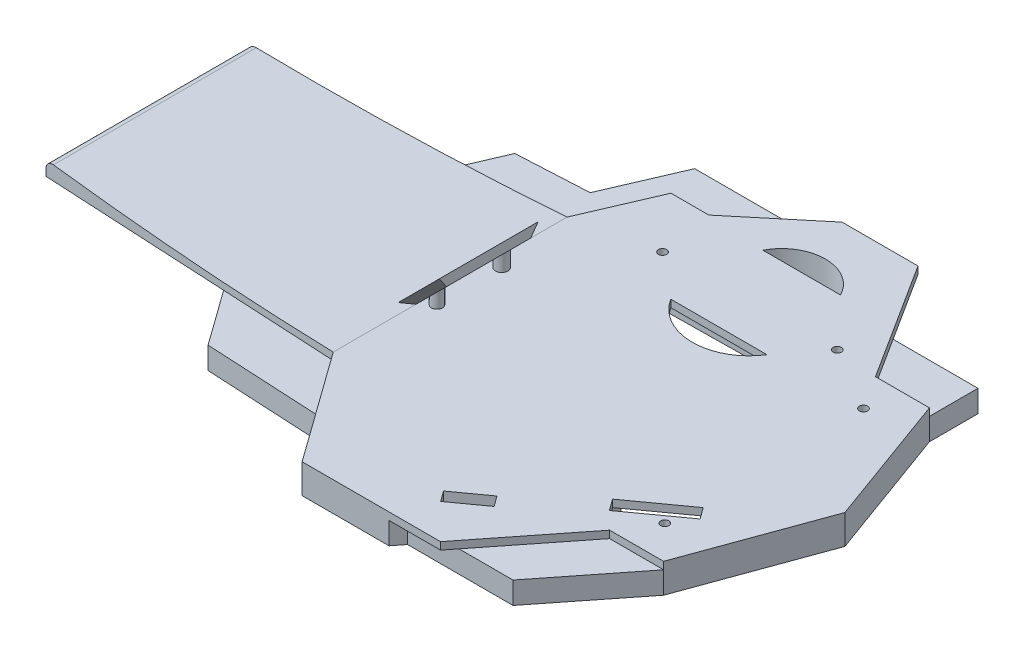
SolidWorks part; units mm, degrees
ref_plane "前视基准面" through (0, 0, 0) normal (0, 0, 1) x (1, 0, 0)
ref_plane "上视基准面" through (0, 0, 0) normal (0, 1, 0) x (1, 0, 0)
ref_plane "右视基准面" through (0, 0, 0) normal (1, 0, 0) x (0, 0, -1)
other "Configuration Table"
sketch "草图2" plane through (0, 0, 0) normal (0, 1, 0) x (1, 0, 0)
  line L0 (0, 0) -> (243.6421, 0) construction
  line L30 (176.8295, 36.1855) -> (82.5273, -31.8251) construction
  line L35 (141.8216, 68.0827) -> (121.1619, 68.0827)
  line L36 (176.8295, 36.1855) -> (190, 0)
  line L37 (104.1466, -61.9173) -> (82.5273, -31.8251)
  line L38 (82.5273, -31.8251) -> (0, -27.5)
  line L39 (0, -27.5) -> (0, 27.5)
  line L40 (0, 27.5) -> (82.5273, 31.8251)
  line L43 (190, 0) -> (176.8295, -36.1855)
  line L45 (82.5273, 31.8251) -> (91.0398, 51.6089)
  line L51 (104.1466, -61.9173) -> (190, 0) construction
  line L53 (141.8216, -61.9173) -> (104.1466, -61.9173)
  line L55 (82.5273, 31.8251) -> (342.4089, 31.8251) construction
  line L57 (176.8295, 36.1855) -> (176.8295, 0) construction
  line L58 (176.8295, 0) -> (176.8295, -36.1855) construction
  line L59 (82.5273, -31.8251) -> (342.4089, -31.8251) construction
  line L62 (91.0398, 51.6089) -> (101.351, 51.6089)
  line L63 (101.351, 51.6089) -> (121.1619, 68.0827)
  line L64 (141.8216, 68.0827) -> (162.1337, 36.1855)
  line L65 (162.1337, 36.1855) -> (176.8295, 36.1855)
  line L66 (176.8295, -36.1855) -> (162.1337, -36.1855)
  line L67 (162.1337, -36.1855) -> (141.8216, -61.9173)
  dimension "D1" = 190
  dimension "D2" = 130
  dimension "D4" = 55
  dimension "D6" = 93
  dimension "D7" = 93
  dimension "D8" = 140
extrude "凸台-拉伸1" add sketch "草图2" along normal blind 2
sketch "草图6" plane through (0, 2, 0) normal (0, 1, 0) x (1, 0, 0)
  line L0 (82.5273, 31.8251) -> (82.5273, -31.8251)
  line L1 (82.5273, -31.8251) -> (0, -27.5)
  line L2 (0, -27.5) -> (0, 27.5)
  line L3 (0, 27.5) -> (82.5273, 31.8251)
extrude "凸台-拉伸2" add sketch "草图6" along normal blind 2
sketch "草图7" plane through (0, 0, 0) normal (0, 0, 1) x (1, 0, 0)
  line L2 (82.5273, 2) -> (82.5273, 30.7408)
  line L3 (82.5273, 30.7408) -> (0, 4)
  spline S0 degree 2 poles (82.5273, 2) (41.2153, 1.0012) (0, 4) knots 0 0 0 1 1 1
extrude "切除-拉伸3" cut sketch "草图7" against normal through all both and the other way through all
fillet "圆角1" radius 2 1 edges at (0, 4, 0)
ref_plane "基准面3" through (0, -12, 0) normal (0, -1, 0) x (-1, 0, 0)
sketch "草图10" plane through (0, 0, 0) normal (0, -1, 0) x (1, 0, 0)
  line L0 (0, 27.5) -> (82.5273, 31.8251)
  line L1 (82.5273, 31.8251) -> (171.8529, 31.8251)
  line L2 (171.8529, 31.8251) -> (171.8529, -31.8251)
  line L3 (171.8529, -31.8251) -> (82.5273, -31.8251)
  line L4 (82.5273, -31.8251) -> (0, -27.5)
  line L5 (0, -27.5) -> (0, 27.5)
sketch "草图12" plane through (0, 2, 0) normal (0, 1, 0) x (1, 0, 0)
  line L0 (176.8295, 36.1855) -> (82.5273, -31.8251)
  line L1 (190, 0) -> (104.1466, -61.9173)
  line L2 (183.4148, 18.0928) -> (93.337, -46.8712) construction
  line L3 (190, 0) -> (176.8295, 36.1855) construction
  line L4 (82.5273, -31.8251) -> (104.1466, -61.9173) construction
sketch "草图13" plane through (0, 0, 0) normal (0, -1, 0) x (1, 0, 0)
  line L0 (53.5015, -30.3039) -> (58.4123, -41.717)
  line L1 (82.5273, -31.8251) -> (0, -27.5) construction
  line L2 (58.4123, -41.717) -> (77.9269, -42.7397)
  line L3 (77.9269, -42.7397) -> (86.4844, -62.6282)
  line L4 (86.4844, -62.6282) -> (136.1647, -62.6282)
  line L5 (176.8295, 36.1855) -> (190, 0)
  line L6 (190, 0) -> (176.8295, -36.1855)
  line L7 (136.1647, -62.6282) -> (144.5841, -49.4069)
  line L8 (144.5841, -49.4069) -> (176.8295, -49.4069)
  line L9 (176.8295, -49.4069) -> (176.8295, -36.1855)
  line L11 (176.8295, 36.1855) -> (158.7432, 59.0976)
  line L12 (158.7432, 59.0976) -> (130.0164, 59.0976)
  line L13 (130.0164, 59.0976) -> (127.7906, 61.9173)
  line L14 (104.1466, 61.9173) -> (141.8216, 61.9173) construction
  line L15 (127.7906, 61.9173) -> (104.1466, 61.9173)
  line L16 (104.1466, 61.9173) -> (93.337, 46.8712)
  line L17 (93.337, 46.8712) -> (61.8459, 45.2208)
  line L18 (61.8459, 45.2208) -> (51.0363, 30.1747)
  line L19 (0, 27.5) -> (82.5273, 31.8251) construction
  line L20 (51.0363, 30.1747) -> (171.8529, 31.8251)
  line L21 (171.8529, 31.8251) -> (171.8529, -31.8251)
  line L22 (171.8529, -31.8251) -> (53.5015, -30.3039)
extrude "凸台-拉伸4" add sketch "草图13" along normal blind 6 contours L18 L20 L21 L22 L0 L2 L3 L4 L7 L8 L9 L6 L5 L11 L12 L13 L15 L16 L17
sketch "草图17" plane through (0, 2, 0) normal (0, 1, 0) x (1, 0, 0)
  line L3 (116.0112, 26.5953) -> (142.1812, 26.5953)
  line L4 (138.1274, 50.6813) -> (116.9896, 50.6813)
  arc A1 (116.0112, 26.5953) -> (142.1812, 26.5953) centre (129.0962, 34.7996) ccw
  arc A2 (116.9896, 50.6813) -> (138.1274, 50.6813) centre (127.5585, 45.2443) cw
sketch "草图18" plane through (0, 2, 0) normal (0, 1, 0) x (1, 0, 0)
  line L4 (169.5639, -18.1259) -> (155.2183, -28.4719)
  line L5 (171.8094, -21.2395) -> (169.5639, -18.1259)
  line L6 (157.4639, -31.5855) -> (171.8094, -21.2395)
  line L7 (155.2183, -28.4719) -> (157.4639, -31.5855)
  line L8 (169.5639, -18.1259) -> (155.2183, -28.4719)
  line L9 (171.8094, -21.2395) -> (169.5639, -18.1259)
  line L10 (157.4639, -31.5855) -> (171.8094, -21.2395)
  line L11 (155.2183, -28.4719) -> (157.4639, -31.5855)
  line L12 (130.3021, -49.5646) -> (132.3616, -52.4203)
  line L13 (132.3616, -52.4203) -> (140.8147, -46.3239)
  line L14 (140.8147, -46.3239) -> (138.7552, -43.4683)
  line L15 (138.7552, -43.4683) -> (130.3021, -49.5646)
  line L16 (130.3021, -49.5646) -> (132.3616, -52.4203)
  line L17 (132.3616, -52.4203) -> (140.8147, -46.3239)
  line L18 (140.8147, -46.3239) -> (138.7552, -43.4683)
  line L19 (138.7552, -43.4683) -> (130.3021, -49.5646)
  dimension "D1" = 0
  dimension "D2" = 0
extrude "切除-拉伸7" cut sketch "草图18" against normal through all
sketch "草图19" plane through (0, 2, 0) normal (0, 1, 0) x (1, 0, 0)
  line L0 (82.5273, -31.8251) -> (176.8295, 36.1855)
  line L1 (176.8295, 36.1855) -> (190, 0)
  line L2 (190, 0) -> (104.1466, -61.9173)
  line L3 (104.1466, -61.9173) -> (82.5273, -31.8251)
ref_plane "基准面4" through (40.2637, -40.2637, 0) normal (-0.7071, 0.7071, 0) x (0, 0, -1)
sketch "草图23" plane through (40.2637, -40.2637, 0) normal (-0.7071, 0.7071, 0) x (0, 0, -1)
  line L0 (-9.292, -59.7699) -> (13.6381, -59.7699)
  line L1 (-31.8251, -59.7699) -> (31.8251, -59.7699) construction
  line L2 (13.6381, -59.7699) -> (13.6381, -71.5206)
  line L3 (13.6381, -71.5206) -> (-9.292, -71.5206)
  line L4 (-9.292, -71.5206) -> (-9.292, -60.8098)
  line L5 (-9.292, -60.8098) -> (-9.292, -59.7699)
extrude "凸台-拉伸5" add sketch "草图23" along normal blind 2 draft 45 separate body draft outward yes
sketch "草图24" plane through (0, 2, 0) normal (0, 1, 0) x (1, 0, 0)
  circle A0 centre (85.4903, 11.0478) radius 1.6973
  circle A1 centre (85.4903, -6.5413) radius 1.5
extrude "凸台-拉伸11" add sketch "草图24" along normal up to surface (2.9629 mm away) separate body contours A0 | A1 region at (85.4903, 2, -11.0478) region at (85.4903, 2, 6.5413) up to face at (86.6818, 6.1545, -2.173)
ref_plane "基准面6" through (0, 4, 0) normal (0, 1, 0) x (1, 0, 0)
sketch "草图25" plane through (0, 4, 0) normal (0, 1, 0) x (1, 0, 0)
  line L1 (67.0613, -53.2409) -> (67.0613, 49.4655) construction
  line L2 (-9.3986, 0) -> (224.1358, 0) construction
  circle A0 centre (67.0613, -25.5664) radius 3
  circle A1 centre (67.0613, 25.5664) radius 3
  circle A2 centre (168.0155, 27.0476) radius 1
  circle A3 centre (168.0155, -27.0476) radius 1
  circle A4 centre (150.7888, 25.9399) radius 3
  circle A5 centre (150.7888, -25.9399) radius 3
  point P11 (168.0155, 27.0476)
  point P14 (168.0155, -27.0476)
extrude "切除-拉伸8" cut sketch "草图17" against normal through all contours L4 A2 | L4 A2 | A1 L3 | A1 L3 region at (129.0962, 2, -23.6319) region at (127.5585, 2, -53.332)
hole_wizard "#4-40 螺纹孔3" positions "草图25" profile "草图26" tap size "#4-40" standard "ANSI Inch" end condition through all
sketch "草图26" plane through (168.0155, 4, 27.0476) normal (1, 0, 0) x (0, 0, 1)
  line L0 (0, 0) -> (0, 10)
  line L1 (0, 10) -> (1.1303, 10)
  line L2 (1.1303, 10) -> (1.1303, 0)
  line L5 (1.1303, 0) -> (0, 0)
  line L11 (0, -6.35) -> (0, 107.95) construction
  dimension "通孔螺纹孔钻头直径" = 2.2606
  dimension "通孔螺纹孔钻头深度" = 10
cosmetic thread "孔螺纹线4" parameters "D2"=2.8448
cosmetic thread "孔螺纹线5" parameters "D2"=2.8448
sketch "草图29" plane through (0, 0, 0) normal (0, -1, 0) x (1, 0, 0)
  circle A0 centre (67.0613, 25.5664) radius 3
  circle A1 centre (67.0613, -25.5664) radius 3
  circle A2 centre (150.7888, 25.9399) radius 3
  circle A3 centre (150.7888, -25.9399) radius 3
extrude "凸台-拉伸14" add sketch "草图29" along normal blind 5 contours A0 | A1 | A2 | A3 region at (67.0613, 0, 25.5664) region at (67.0613, 0, -25.5664) region at (150.7888, 0, 25.9399) region at (150.7888, 0, -25.9399)
sketch "草图33" plane through (0, 2, 0) normal (0, 1, 0) x (1, 0, 0)
  point P0 (150.5968, 37.3344)
  point P3 (103.7494, 36.6082)
hole_wizard "#4-40 螺纹孔4" positions "草图33" profile "草图32" tap size "#4-40" standard "ANSI Inch" end condition through all
sketch "草图32" plane through (150.5968, 2, -37.3344) normal (1, 0, 0) x (0, 0, 1)
  line L0 (0, 0) -> (0, 8)
  line L1 (0, 8) -> (1.1303, 8)
  line L2 (1.1303, 8) -> (1.1303, 0)
  line L5 (1.1303, 0) -> (0, 0)
  line L11 (0, -6.35) -> (0, 107.95) construction
  dimension "通孔螺纹孔钻头直径" = 2.2606
  dimension "通孔螺纹孔钻头深度" = 8
cosmetic thread "孔螺纹线8" parameters "D2"=2.8448
cosmetic thread "孔螺纹线9" parameters "D2"=2.8448
sketch "草图36" plane through (0, 0, 0) normal (0, 1, 0) x (1, 0, 0)
  point P0 (176.7356, -15.6397)
  point P3 (122.1817, -55.0926)
hole_wizard "#4-40 螺纹孔5" positions "草图36" profile "草图35" tap size "#4-40" standard "ANSI Inch" end condition through all
sketch "草图35" plane through (176.7356, 0, 15.6397) normal (1, 0, 0) x (0, 0, 1)
  line L0 (0, 0) -> (0, 6)
  line L1 (0, 6) -> (1.1303, 6)
  line L2 (1.1303, 6) -> (1.1303, 0)
  line L5 (1.1303, 0) -> (0, 0)
  line L11 (0, -6.35) -> (0, 107.95) construction
  dimension "通孔螺纹孔钻头直径" = 2.2606
  dimension "通孔螺纹孔钻头深度" = 6
cosmetic thread "孔螺纹线10" parameters "D2"=2.8448
cosmetic thread "孔螺纹线11" parameters "D2"=2.8448
